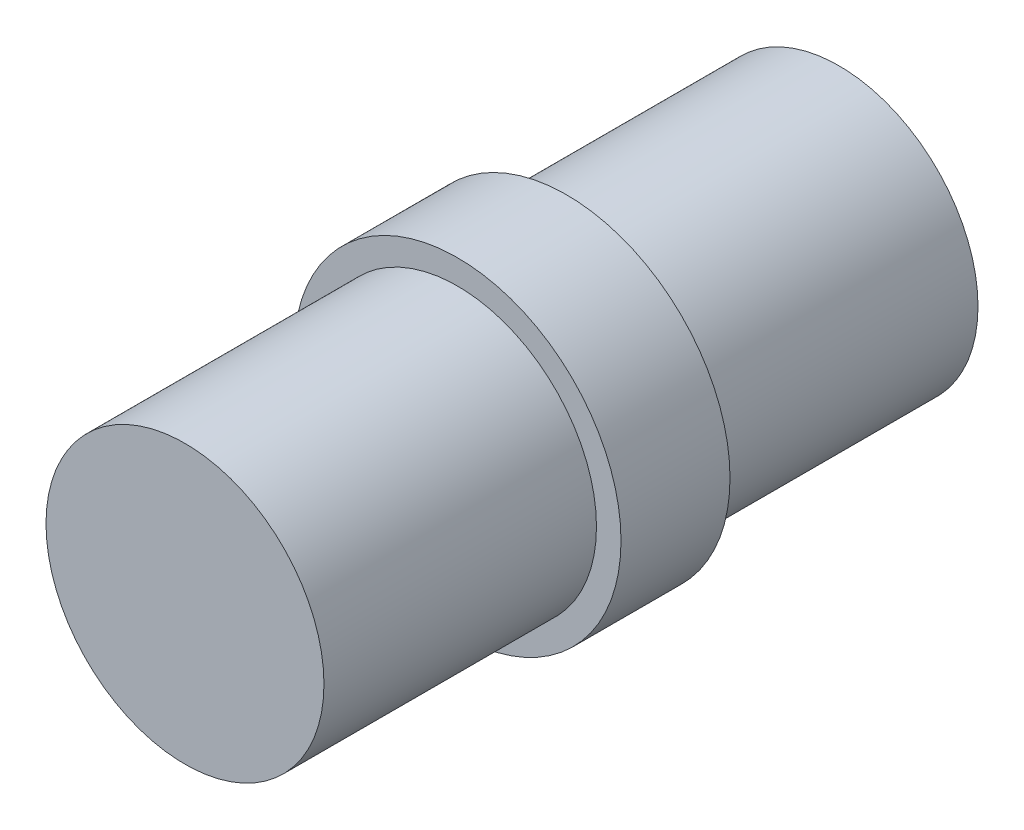
SolidWorks part; units mm, degrees
ref_plane "Front Plane" through (0, 0, 0) normal (0, 0, 1) x (1, 0, 0)
ref_plane "Top Plane" through (0, 0, 0) normal (0, 1, 0) x (1, 0, 0)
ref_plane "Right Plane" through (0, 0, 0) normal (1, 0, 0) x (0, 0, -1)
sketch "Sketch1" plane through (0, 0, 0) normal (0, 0, 1) x (1, 0, 0)
  circle A0 centre (0, 0) radius 2.55
  dimension "D1" = 5.1
extrude "Boss-Extrude1" add sketch "Sketch1" along normal blind 5
sketch "Sketch2" plane through (0, 0, 0) normal (0, 0, 1) x (1, 0, 0)
  circle A0 centre (0, 0) radius 3
  dimension "D1" = 6
extrude "Boss-Extrude2" add sketch "Sketch2" against normal blind 2
extrude "Boss-Extrude3" add sketch "Sketch1<2>" against normal blind 5 from surface starting at face at (3, 0, -2)
sketch "Sketch1<2>" plane through (0, 0, 0) normal (0, 0, 1) x (1, 0, 0) same geometry as "Sketch1"
